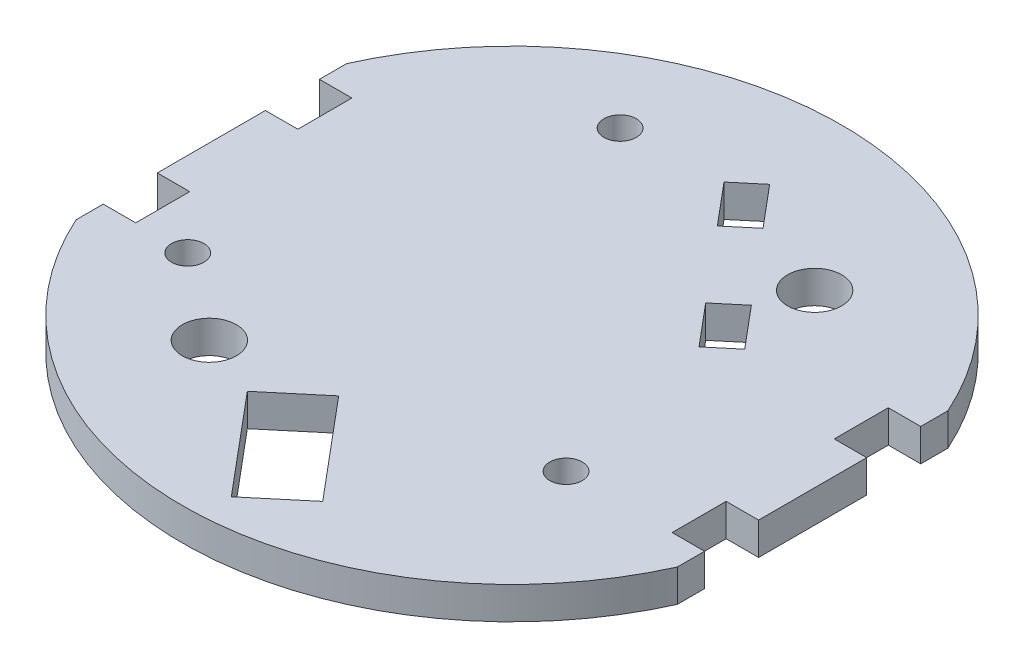
SolidWorks part; units mm, degrees
ref_plane "Alzado" through (0, 0, 0) normal (0, 0, 1) x (1, 0, 0)
ref_plane "Planta" through (0, 0, 0) normal (0, 1, 0) x (1, 0, 0)
ref_plane "Vista lateral" through (0, 0, 0) normal (1, 0, 0) x (0, 0, -1)
sketch "Croquis1" plane through (0, 0, 0) normal (0, 1, 0) x (1, 0, 0)
  circle A0 centre (0, 0) radius 30.5
extrude "Saliente-Extruir1" add sketch "Croquis1" along normal blind 3
sketch "Croquis5" plane through (0, 3, 0) normal (0, 1, 0) x (1, 0, 0)
  line L0 (0, 0) -> (0, 10)
  line L1 (28.8141, -5) -> (30.0874, -5)
  line L2 (28.8141, 5) -> (30.0874, 5)
  line L3 (-24.8141, 10) -> (-28.8141, 10)
  line L4 (24.8141, -5) -> (24.8141, -10)
  line L5 (-24.8141, -10) -> (-28.8141, -10)
  line L6 (24.8141, -5) -> (28.8141, -5)
  line L7 (24.8141, 5) -> (24.8141, 10)
  line L8 (-24.8141, 5) -> (-28.8141, 5)
  line L9 (-24.8141, 5) -> (-24.8141, 10)
  line L10 (-24.8141, -5) -> (-28.8141, -5)
  line L11 (-24.8141, -5) -> (-24.8141, -10)
  line L12 (24.8141, 5) -> (28.8141, 5)
  line L13 (24.8141, -10) -> (28.8141, -10)
  line L14 (24.8141, 10) -> (28.8141, 10)
  line L15 (-28.8141, 5) -> (-30.0874, 5)
  line L16 (-28.8141, -5) -> (-30.0874, -5)
  circle A1 centre (0, 0) radius 30.5 construction
  arc A2 (-28.8141, 10) -> (-30.0874, 5) centre (0, 0) ccw
  arc A3 (28.8141, 10) -> (28.8141, -10) centre (0, 0) cw
  arc A4 (-30.0874, -5) -> (-28.8141, -10) centre (0, 0) ccw
  arc A5 (30.0874, -5) -> (28.8141, -10) centre (0, 0) cw
  arc A6 (28.8141, 10) -> (30.0874, 5) centre (0, 0) cw
  circle M2 centre (0, 0) radius 30.5
extrude "Cortar-Extruir3" cut sketch "Croquis5" against normal blind 4 contours L11 L10 L8 L9 L3 L5 M2 | L15 L8 L9 L3 M2 | L14 L7 L12 L2 M2 | L4 L13 L1 L6 M2 region at (27.1844, 3, 7.3876) region at (27.1844, 3, -7.3876) region at (-27.1844, 3, 7.3876) region at (-27.1844, 3, -7.3876)
sketch "Croquis7" plane through (0, 3, 0) normal (0, 1, 0) x (1, 0, 0)
  line L0 (-8.1011, 29.1011) -> (9.5756, 8.0348)
  line L1 (9.5756, 8.0348) -> (27.2522, -13.0314)
  line L2 (-8.1011, 29.1011) -> (-27.2522, 13.0314)
  line L3 (27.2522, -13.0314) -> (8.1011, -29.1011)
  line L4 (8.1011, -29.1011) -> (-27.2522, 13.0314)
  line L5 (1.4284, 22.4114) -> (-0.8697, 20.4831)
  line L6 (1.4284, 22.4114) -> (4.6423, 18.5812)
  line L7 (4.6423, 18.5812) -> (2.3442, 16.6528)
  line L8 (2.3442, 16.6528) -> (-0.8697, 20.4831)
  line L9 (7.9686, 9.95) -> (11.1825, 6.1197)
  line L10 (8.1011, -29.1011) -> (5.53, -26.0369)
  line L11 (10.2667, 11.8783) -> (13.4807, 8.0481)
  line L12 (13.4807, 8.0481) -> (11.1825, 6.1197)
  line L13 (10.2667, 11.8783) -> (7.9686, 9.95)
  line L14 (5.53, -26.0369) -> (10.8923, -21.5374)
  line L15 (10.8923, -21.5374) -> (-19.3188, 14.4667)
  line L17 (-24.6811, 9.9672) -> (-19.3188, 14.4667)
  point P7 (-9.5756, -8.0348)
extrude "Cortar-Extruir5" cut sketch "Croquis7" against normal blind 4 contours L7 L6 L5 L0 | L11 L13 L0 L1 L12 region at (1.8863, 3, -19.5321) region at (10.7246, 3, -8.999)
sketch "Croquis8" plane through (0, 3, 0) normal (0, 1, 0) x (1, 0, 0)
  line L0 (-11.3137, 11.3137) -> (0, 0)
  line L2 (0, 0) -> (12, 0)
  line L3 (0, 0) -> (-11.3137, 11.3137)
  line L4 (12, 0) -> (12, 16)
  line L5 (0, 0) -> (-12, 0)
  line L6 (-12, 0) -> (-12, -16)
  line L10 (1.5586, -27.5246) -> (6.1549, -23.6679)
  line L11 (6.1549, -23.6679) -> (-1.5586, -14.4754)
  line L13 (-6.1549, -18.3321) -> (-1.5586, -14.4754)
  line L14 (1.5586, -27.5246) -> (-6.1549, -18.3321)
  circle A0 centre (0, 0) radius 30
  circle A1 centre (0, 0) radius 16
  circle A2 centre (0, 0) radius 24
  circle A3 centre (-12, -16) radius 2.5
  circle A4 centre (0, 0) radius 20
  circle A5 centre (12, 16) radius 2.5
  point P20 (-3.8567, -16.4037)
extrude "Cortar-Extruir6" cut sketch "Croquis8" against normal blind 10 contours L13 A4 L10 L11 | A4 A3 | L6 A4 A3 | A3 A4 L6 | A4 A5 | L4 A5 A4 | A4 A5 L4 | A2 L14 L10 L11 | A4 L14 A2 L11 | L13 A1 L11 region at (10.8019, 3, -15.3654) region at (12.6835, 3, -14.5491) region at (-10.8019, 3, 15.3654) region at (-12.6835, 3, 14.5491) region at (-1.7552, 3, 18.1481) region at (-1.6254, 3, 15.4208) region at (12.6194, 3, -16.8259) region at (-12.6194, 3, 16.8259) region at (0.4942, 3, 21.8146) region at (2.2344, 3, 25.0251)
sketch "Croquis9" plane through (0, 3, 0) normal (0, 1, 0) x (1, 0, 0)
  line L0 (0, 0) -> (0, 20)
  line L1 (0, 20) -> (-10, 20)
  line L2 (0, 0) -> (-20, 0)
  line L3 (-20, 0) -> (-20, -10)
  line L4 (0, 0) -> (15, 0)
  line L5 (15, 0) -> (15, -10)
  circle A0 centre (-10, 20) radius 1.5
  circle A1 centre (-20, -10) radius 1.5
  circle A2 centre (15, -10) radius 1.5
extrude "Cortar-Extruir7" cut sketch "Croquis9" against normal blind 3 contours A1 | A2 | A0 region at (-18.9693, 3, 8.9693) region at (16.0307, 3, 8.9693)
sketch "Croquis10" plane through (0, 3, 0) normal (0, 1, 0) x (1, 0, 0)
  line L0 (-24.8141, 10) -> (-27.8141, 10)
  line L2 (-24.8141, 10) -> (-28.8141, 10) construction
  line L4 (-27.8141, 10) -> (-27.8141, 12.5151)
  line L6 (-27.8141, 10) -> (-28.8141, 10)
  line L9 (-24.8141, 5) -> (-30.0874, 5) construction
  line L10 (-27.8141, 5) -> (-27.8141, -5)
  line L11 (-24.8141, -5) -> (-30.0874, -5) construction
  line L12 (-27.8141, -5) -> (-30.0874, -5)
  line L13 (-27.8141, 5) -> (-30.0874, 5)
  line L14 (-27.8141, -10) -> (-28.8141, -10)
  line L15 (-27.8141, -10) -> (-27.8141, -12.5151)
  line L16 (27.8141, -10) -> (27.8141, -12.5151)
  line L17 (27.8141, -10) -> (28.8141, -10)
  line L18 (27.8141, 5) -> (30.0874, 5)
  line L19 (27.8141, -5) -> (30.0874, -5)
  line L20 (27.8141, 5) -> (27.8141, -5)
  line L21 (27.8141, 10) -> (28.8141, 10)
  line L22 (27.8141, 10) -> (27.8141, 12.5151)
  line L23 (24.8141, 10) -> (27.8141, 10)
  arc A2 (28.8141, 10) -> (-28.8141, 10) centre (0, 0) ccw construction
  arc A5 (-27.8141, 12.5151) -> (-28.8141, 10) centre (0, 0) ccw
  arc A6 (-30.0874, 5) -> (-30.0874, -5) centre (0, 0) ccw
  arc A7 (-27.8141, -12.5151) -> (-28.8141, -10) centre (0, 0) cw
  arc A8 (27.8141, -12.5151) -> (28.8141, -10) centre (0, 0) ccw
  arc A9 (30.0874, 5) -> (30.0874, -5) centre (0, 0) cw
  arc A10 (27.8141, 12.5151) -> (28.8141, 10) centre (0, 0) cw
  line M9 (24.8141, -5) -> (30.0874, -5)
  arc M10 (30.0874, -5) -> (30.0874, 5) centre (0, 0) ccw
  line M11 (30.0874, 5) -> (24.8141, 5)
  line M13 (24.8141, 10) -> (28.8141, 10)
  arc M14 (28.8141, 10) -> (-28.8141, 10) centre (0, 0) ccw
  line M15 (-28.8141, 10) -> (-24.8141, 10)
  line M17 (-24.8141, 5) -> (-30.0874, 5)
  arc M18 (-30.0874, 5) -> (-30.0874, -5) centre (0, 0) ccw
  line M19 (-30.0874, -5) -> (-24.8141, -5)
  line M21 (-24.8141, -10) -> (-28.8141, -10)
  arc M22 (-28.8141, -10) -> (28.8141, -10) centre (0, 0) ccw
  line M23 (28.8141, -10) -> (24.8141, -10)
extrude "Cortar-Extruir8" cut sketch "Croquis10" against normal blind 3 contours L15 M21 M22 | L10 M17 M18 M19 | L4 M15 M14 | L16 M23 M22 | L20 M11 M9 M10 | L22 M13 M14 | L22 A10 L21 region at (-28.1547, 3, -10.8559) region at (28.1547, 3, -10.8559) region at (-29.0914, 3, 0) region at (-28.1547, 3, 10.8559) region at (28.1547, 3, 10.8559) region at (29.0914, 3, 0)
sketch "Croquis11" plane through (0, 3, 0) normal (0, 1, 0) x (1, 0, 0)
  line L1 (13.7002, 20.3114) -> (28.7604, 10.1532)
  line L2 (13.7002, 20.3114) -> (-1.36, 30.4697)
  arc A0 (27.8141, 12.5151) -> (-27.8141, 12.5151) centre (0, 0) ccw construction
  arc A1 (-27.8141, -12.5151) -> (27.8141, -12.5151) centre (0, 0) ccw construction
